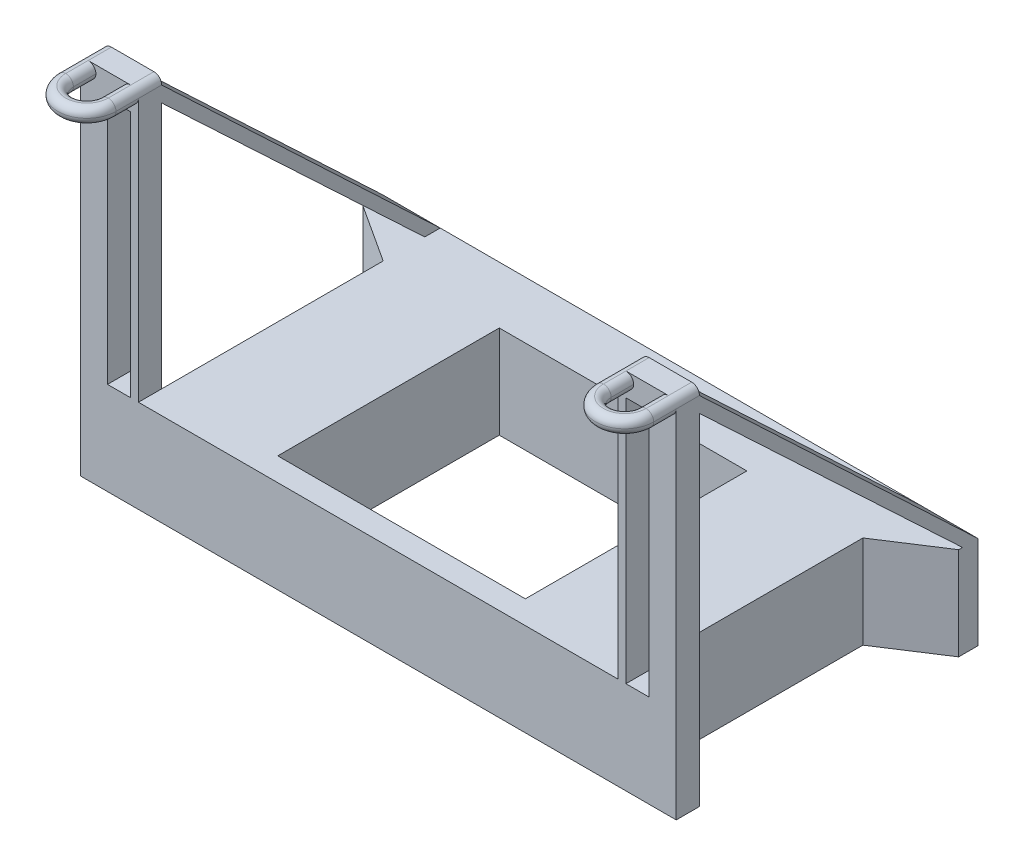
SolidWorks part; units mm, degrees
ref_plane "Plan de face" through (0, 0, 0) normal (0, 0, 1) x (1, 0, 0)
ref_plane "Plan de dessus" through (0, 0, 0) normal (0, 1, 0) x (1, 0, 0)
ref_plane "Plan de droite" through (0, 0, 0) normal (1, 0, 0) x (0, 0, -1)
sketch "Esquisse1" plane through (0, 0, 0) normal (0, 0, 1) x (1, 0, 0)
  line L0 (-38.5, 0) -> (0, 0)
  line L4 (-38.5, 0) -> (-38.5, 47)
  line L6 (-38.5, 47) -> (-31, 47)
  line L7 (-31, 47) -> (-31, 12)
  line L8 (-31, 12) -> (0, 12)
  line L9 (0, 12) -> (0, 0)
  dimension "D1" = 31
  dimension "D3" = 12
  dimension "D4" = 7.5
extrude "Boss.-Extru.1" add sketch "Esquisse1" along normal blind 39 contours L0 L9 L8 L7 L6 L4
sketch "Esquisse2" plane through (-31, 0, 0) normal (1, 0, 0) x (0, 0, -1)
  line L0 (-39, 47) -> (0, 47) construction
  line L1 (-36, 47) -> (0, 47)
  line L2 (-36, 47) -> (-36, 12)
  line L3 (-36, 12) -> (0, 12)
  line L4 (0, 47) -> (0, 12)
  line L5 (-39, 47) -> (-39, 12) construction
  dimension "D1" = 3
extrude "Enlèv. mat.-Extru.1" cut sketch "Esquisse2" against normal through all contours L2 L3 L4 L1
sketch "Esquisse3" plane through (0, 0, 36) normal (0, 0, -1) x (-1, 0, 0)
  line L1 (32, 44) -> (35, 44)
  line L2 (32, 44) -> (32, 12)
  line L3 (32, 12) -> (35, 12)
  line L4 (35, 44) -> (35, 12)
  line L5 (38.5, 12) -> (0, 12) construction
  line L6 (38.5, 47) -> (38.5, 12) construction
  line L9 (38.5, 47) -> (31, 47) construction
  dimension "D1" = 3
  dimension "D2" = 3.5
  dimension "D3" = 3
extrude "Enlèv. mat.-Extru.2" cut sketch "Esquisse3" against normal blind 39 and the other way blind 7.5
sketch "Esquisse5" plane through (0, 12, 0) normal (0, 1, 0) x (1, 0, 0)
  line L0 (-38.5, 0) -> (0, 0) construction
  line L1 (-31, -36) -> (-38.5, -36)
  line L2 (-31, -36) -> (-31, -7.5)
  line L3 (-31, -7.5) -> (-38.5, -7.5)
  line L4 (-38.5, -36) -> (-38.5, -7.5)
  point P8 (-38.5, -36)
  dimension "D1" = 7.5
  dimension "D2" = 7.5
extrude "Enlèv. mat.-Extru.3" cut sketch "Esquisse5" against normal through all
sketch "Esquisse6" plane through (0, 0, 39) normal (0, 0, 1) x (1, 0, 0)
  line L1 (-38.5, 47) -> (-36.5, 47)
  line L2 (-38.5, 47) -> (-38.5, 45)
  line L3 (-38.5, 45) -> (-36.5, 45)
  line L4 (-36.5, 47) -> (-36.5, 45)
  dimension "D1" = 2
  dimension "D2" = 2
sketch "Esquisse7" plane through (0, 47, 0) normal (0, 1, 0) x (1, 0, 0)
  line L0 (-37.5, -39) -> (-37.5, -41.9037)
  line L1 (-38.5, -39) -> (-36.5, -39) construction
  line L2 (-32, -39) -> (-32, -41.9037)
  arc A0 (-37.5, -41.9037) -> (-32, -41.9037) centre (-34.75, -41.9037) ccw
  dimension "D1" = 1
sweep "Balayage3" add profiles "Esquisse6" path "Esquisse7"
fillet "Congé2" radius 1 12 edges at (-31, 45, 40.4519) (-38.5, 45, 40.4519) (-31, 47, 38.9519) (-38.5, 47, 38.9519) (-34.75, 45, 45.6537) (-34.75, 47, 45.6537) (-36.5, 47, 40.4519) (-33, 47, 40.4519) (-34.75, 47, 43.6537) (-36.5, 45, 40.4519) (-34.75, 45, 43.6537) (-33, 45, 40.4519)
sketch "Esquisse8" plane through (-38.5, 0, 0) normal (-1, 0, 0) x (0, 0, 1)
  line L0 (36, 46) -> (0, 12)
  line L1 (0, 12) -> (2, 12)
  line L2 (2, 12) -> (36, 44)
  line L3 (36, 46) -> (36, 0) construction
  line L4 (7.5, 12) -> (0, 12) construction
  line L5 (36, 46) -> (36, 44)
  dimension "D1" = 2
extrude "Boss.-Extru.3" add sketch "Esquisse8" against normal blind 7.5 contours L0 L1 L2 L5
chamfer "Chanfrein1" distance 5 angle 57 1 edges at (-38.5, 6, 7.5) first distance on face at (-38.5, 17.2, 20.3)
sketch "Esquisse9" plane through (0, 0, 0) normal (0, -1, 0) x (1, 0, 0)
  line L0 (-31, 36) -> (-31, 7.3706) construction
  line L1 (-26, 36) -> (-21, 36)
  line L2 (-26, 36) -> (-26, 7.3706)
  line L3 (-26, 7.3706) -> (-21, 7.3706)
  line L4 (-21, 36) -> (-21, 7.3706)
  point P5 (-31, 7.3706)
  dimension "D1" = 5
  dimension "D2" = 5
extrude "Enlèv. mat.-Extru.4" cut sketch "Esquisse9" against normal blind 6
sketch "Esquisse10" plane through (0, 0, 0) normal (0, -1, 0) x (1, 0, 0)
  line L0 (0, 39) -> (0, 0) construction
  line L1 (0, 36) -> (-16, 36)
  line L2 (0, 36) -> (0, 7.3706)
  line L3 (0, 7.3706) -> (-16, 7.3706)
  line L4 (-16, 36) -> (-16, 7.3706)
  line L5 (-21, 7.3706) -> (-21, 36) construction
  point P8 (0, 0)
  point P10 (0, 0)
  dimension "D1" = 5
extrude "Enlèv. mat.-Extru.6" cut sketch "Esquisse10" against normal through all
mirror "Symétrie1" about plane through (0, 12, 39) normal (1, 0, 0) of bodies 111 103
